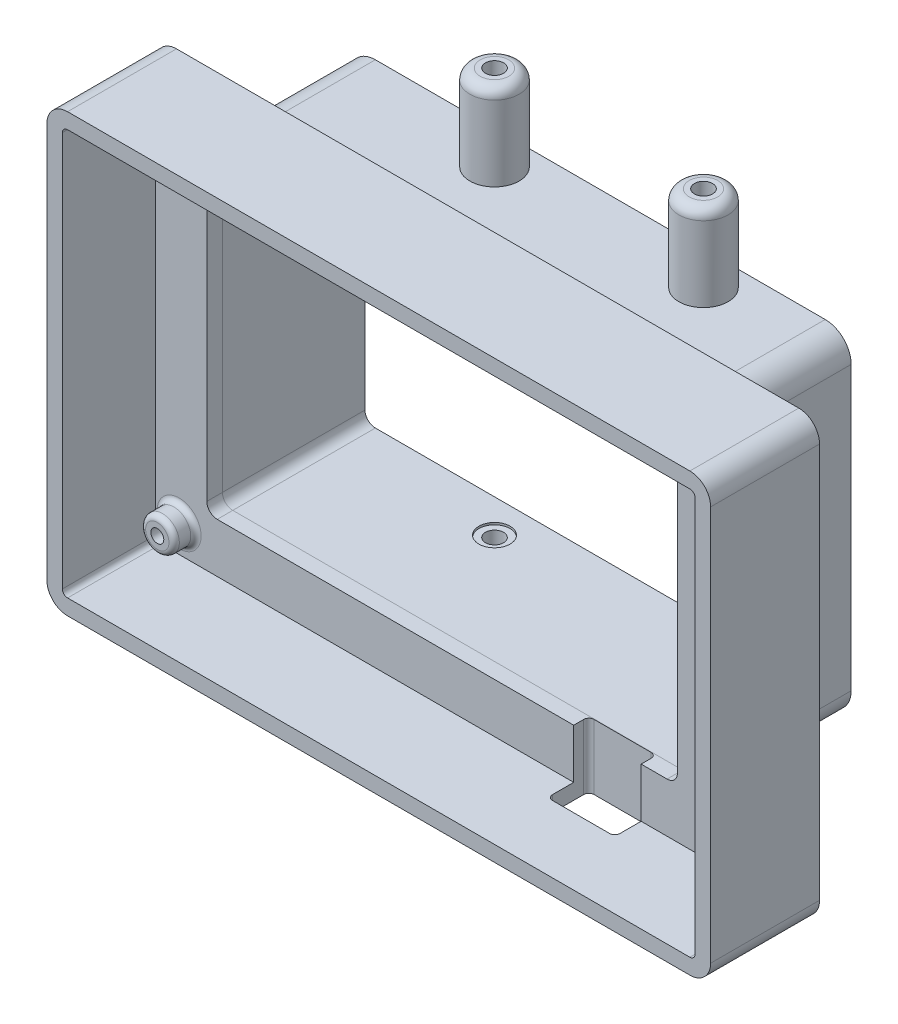
SolidWorks part; units mm, degrees
note: The reader was unsure of these and kept them because the rebuilt part matched: shared geometry of "Esquisse1<3>", "Esquisse3<2>", "Esquisse3<3>", "Esquisse4<5>".
ref_plane "Plan de face" through (0, 0, 0) normal (0, 0, 1) x (1, 0, 0)
ref_plane "Plan de dessus" through (0, 0, 0) normal (0, 1, 0) x (1, 0, 0)
ref_plane "Plan de droite" through (0, 0, 0) normal (1, 0, 0) x (0, 0, -1)
sketch "Esquisse1" plane through (0, 0, 0) normal (0, 0, 1) x (1, 0, 0)
  line L0 (0, 0) -> (0, 39.1) construction
  line L1 (-61, 39.1) -> (61, 39.1)
  line L2 (-61, 39.1) -> (-61, -39.1)
  line L3 (-61, -39.1) -> (61, -39.1)
  line L4 (61, 39.1) -> (61, -39.1)
  line L5 (0, 0) -> (-61, 0) construction
  line L7 (-56.5, 33.9) -> (56.5, 33.9) construction
  line L8 (-56.5, 33.9) -> (-56.5, -33.9) construction
  line L9 (-56.5, -33.9) -> (56.5, -33.9) construction
  line L10 (56.5, 33.9) -> (56.5, -33.9) construction
  circle A0 centre (-56.5, 33.9) radius 1.25
  circle A1 centre (-56.5, -33.9) radius 1.25
  circle A2 centre (56.5, -33.9) radius 1.25
  circle A3 centre (56.5, 33.9) radius 1.25
  circle A4 centre (-56.5, 33.9) radius 3.25
  circle A5 centre (-56.5, -33.9) radius 3.25
  circle A6 centre (56.5, -33.9) radius 3.25
  circle A7 centre (56.5, 33.9) radius 3.25
  point P4 (0, 39.1)
  point P6 (-61, 0)
  dimension "D5" = 2.5
  dimension "D6" = 6.5
  dimension "D1" = 78.2
  dimension "D2" = 122
  dimension "D3" = 67.8
  dimension "D4" = 113
extrude "Boss.-Extru.1" add sketch "Esquisse1" along normal blind 18 contours L4 L1 L2 L3 A5 A4 A6 A7
shell "Coque1" thickness 3
extrude "Enlèv. mat.-Extru.1" cut sketch "Esquisse1<3>" along normal up to next and the other way up to next contours A1 | A2 | A3 | A0
sketch "Esquisse1<3>" plane through (0, 0, 0) normal (0, 0, 1) x (1, 0, 0) same geometry as "Esquisse1"
sketch "Esquisse2" plane through (0, 0, 18) normal (0, 0, 1) x (1, 0, 0)
  circle A0 centre (-56.5, 33.9) radius 3.25
  circle A1 centre (-56.5, 33.9) radius 3.25 construction
  circle A2 centre (56.5, 33.9) radius 3.25
  circle A3 centre (56.5, -33.9) radius 3.25
  circle A4 centre (-56.5, -33.9) radius 3.25
  circle A5 centre (-56.5, -33.9) radius 3.25 construction
  circle A6 centre (56.5, 33.9) radius 3.25 construction
  circle A7 centre (56.5, -33.9) radius 3.25 construction
extrude "Enlèv. mat.-Extru.2" cut sketch "Esquisse2" against normal blind 13.8
sketch "Esquisse3" plane through (0, 0, -3) normal (0, 0, -1) x (-1, 0, 0)
  line L0 (51.15, 0) -> (64, 0) construction
  line L1 (-39.6, 28.95) -> (51.15, 28.95)
  line L2 (-39.6, 28.95) -> (-39.6, -29.55)
  line L3 (-39.6, -29.55) -> (51.15, -29.55)
  line L4 (51.15, 28.95) -> (51.15, -29.55)
  line L5 (64, 42.1) -> (64, -42.1) construction
  line L6 (5.775, 28.95) -> (5.775, 42.1) construction
  line L7 (64, 42.1) -> (-64, 42.1) construction
  dimension "D1" = 13.15
  dimension "D2" = 12.85
  dimension "D3" = 90.75
  dimension "D4" = 58.5
extrude "Boss.-Extru.2" add sketch "Esquisse3" along normal blind 24.5
extrude "Enlèv. mat.-Extru.3" cut sketch "Esquisse3<2>" against normal up to next
sketch "Esquisse3<2>" plane through (0, 0, -3) normal (0, 0, -1) x (-1, 0, 0) same geometry as "Esquisse3"
shell "Coque2" thickness 3
extrude "Enlèv. mat.-Extru.5" cut sketch "Esquisse3<3>" along normal up to surface (27.5 mm away) up to face at (-5.775, -0.3, -30.5)
sketch "Esquisse3<3>" plane through (0, 0, -3) normal (0, 0, -1) x (-1, 0, 0) same geometry as "Esquisse3"
fillet "Congé1" radius 1 12 edges at (59.75, 33.9, 0) (59.75, -33.9, 0) (-53.25, -33.9, 0) (-53.25, 33.9, 0) (-53.25, 33.9, 4.2) (-53.25, -33.9, 4.2) (59.75, -33.9, 4.2) (59.75, 33.9, 4.2) (61, 39.1, 9) (61, -39.1, 9) (-61, -39.1, 9) (-61, 39.1, 9)
fillet "Congé2" radius 4 4 edges at (-64, 42.1, 7.5) (64, 42.1, 7.5) (64, -42.1, 7.5) (-64, -42.1, 7.5)
fillet "Congé3" radius 2 4 edges at (39.6, -29.55, -16.75) (-51.15, -29.55, -16.75) (-51.15, 28.95, -16.75) (39.6, 28.95, -16.75)
fillet "Congé4" radius 2 4 edges at (-51.15, 28.95, -1.5) (39.6, 28.95, -1.5) (-51.15, -29.55, -1.5) (39.6, -29.55, -1.5)
fillet "Congé5" radius 5 4 edges at (-54.15, -32.55, -16.75) (-54.15, 31.95, -16.75) (42.6, -32.55, -16.75) (42.6, 31.95, -16.75)
chamfer "Chanfrein1" distance 1 angle 45 4 edges at (-55.25, -33.9, -3) (-55.25, 33.9, -3) (57.75, -33.9, -3) (57.75, 33.9, -3)
sketch "Esquisse4" plane through (0, 31.95, 0) normal (0, 1, 0) x (1, 0, 0)
  line L0 (-19.775, 24.1) -> (20.525, 24.1) construction
  line L1 (-49.15, 30.5) -> (37.6, 30.5) construction
  circle A0 centre (-19.775, 24.1) radius 1.75
  circle A1 centre (20.525, 24.1) radius 1.75
  circle A2 centre (-19.775, 24.1) radius 4.75
  circle A3 centre (20.525, 24.1) radius 4.75
  point P8 (-5.775, 30.5)
  dimension "D3" = 3.5
  dimension "D1" = 40.3
  dimension "D2" = 6.4
  dimension "D4" = 14
  dimension "D5" = 3
extrude "Enlèv. mat.-Extru.8" cut sketch "Esquisse4" against normal up to next (3 mm away)
sketch "Esquisse6" plane through (0, 28.95, 0) normal (0, -1, 0) x (1, 0, 0)
  circle A0 centre (-19.775, -24.1) radius 3
  circle A1 centre (20.525, -24.1) radius 3
  circle A2 centre (20.525, -24.1) radius 1.75 construction
  circle A3 centre (-19.775, -24.1) radius 1.75 construction
  dimension "D1" = 6
extrude "Enlèv. mat.-Extru.9" cut sketch "Esquisse6" against normal blind 1
extrude "Boss.-Extru.4" add sketch "Esquisse4<5>" along normal blind 16.5
sketch "Esquisse4<5>" plane through (0, 31.95, 0) normal (0, 1, 0) x (1, 0, 0) same geometry as "Esquisse4"
mirror "Symétrie1" about plane through (0, 0, 0) normal (0, 1, 0) of "Boss.-Extru.4", "Enlèv. mat.-Extru.8", "Enlèv. mat.-Extru.9"
sketch "Esquisse8" plane through (0, -32.55, 0) normal (0, -1, 0) x (1, 0, 0)
  circle A0 centre (-19.775, -24.1) radius 4.75
  circle A1 centre (20.525, -24.1) radius 4.75
  circle A4 centre (20.525, -24.1) radius 4.75 construction
extrude "Boss.-Extru.5" add sketch "Esquisse8" along normal blind 19
sketch "Esquisse9" plane through (0, -51.55, 0) normal (0, -1, 0) x (1, 0, 0)
  circle A0 centre (20.525, -24.1) radius 1.75
  circle A1 centre (20.525, -24.1) radius 1.75 construction
  circle A2 centre (-19.775, -24.1) radius 1.75
  circle A3 centre (-19.775, -24.1) radius 1.75 construction
extrude "Enlèv. mat.-Extru.10" cut sketch "Esquisse9" against normal up to next (19.6 mm away)
fillet "Congé6" radius 2 4 edges at (20.525, 48.45, -19.35) (-19.775, 48.45, -19.35) (-19.775, -51.55, -28.85) (20.525, -51.55, -28.85)
sketch "Esquisse10" plane through (0, -42.1, 0) normal (0, -1, 0) x (1, 0, 0)
  line L0 (-5.775, -3) -> (-5.775, 5.075) construction
  line L1 (37.6, -3) -> (-49.15, -3) construction
  line L2 (-5.775, 5.075) -> (26.1, 5.075) construction
  line L4 (20.6, 5.075) -> (31.6, 5.075)
  line L5 (19.6, 4.075) -> (19.6, -1.925)
  line L6 (20.6, -2.925) -> (31.6, -2.925)
  line L7 (32.6, 4.075) -> (32.6, -1.925)
  arc A0 (31.6, -2.925) -> (32.6, -1.925) centre (31.6, -1.925) ccw
  arc A1 (19.6, -1.925) -> (20.6, -2.925) centre (20.6, -1.925) ccw
  arc A2 (31.6, 5.075) -> (32.6, 4.075) centre (31.6, 4.075) cw
  arc A3 (20.6, 5.075) -> (19.6, 4.075) centre (20.6, 4.075) ccw
  point P12 (32.6, -2.925)
  point P17 (32.6, 5.075)
  point P20 (19.6, 5.075)
  dimension "D5" = 1
  dimension "D1" = 31.875
  dimension "D2" = 8.075
  dimension "D3" = 13
  dimension "D4" = 8
extrude "Enlèv. mat.-Extru.11" cut sketch "Esquisse10" against normal up to next
